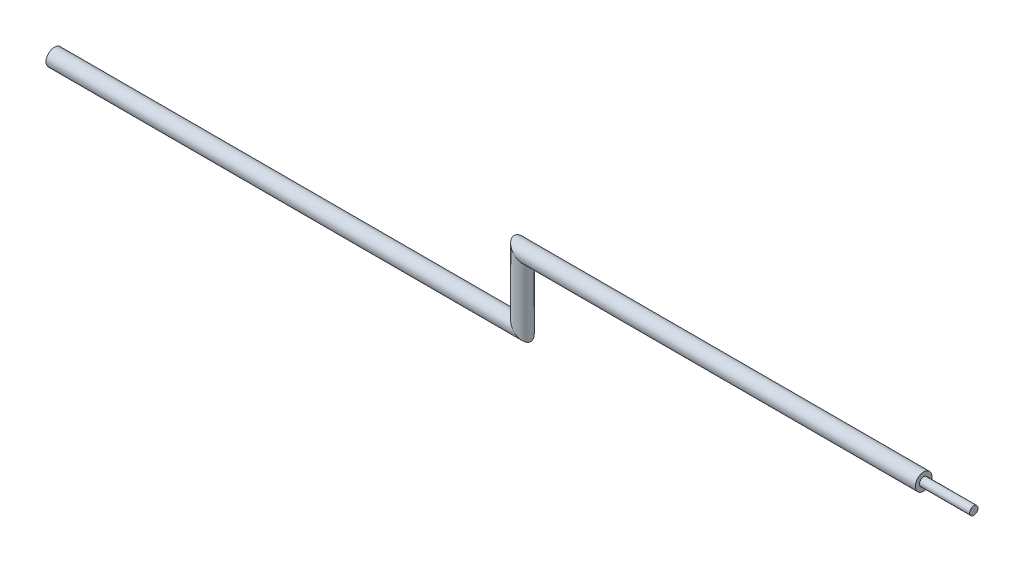
SolidWorks part; units mm, degrees
ref_plane "Front Plane" through (0, 0, 0) normal (0, 0, 1) x (1, 0, 0)
ref_plane "Top Plane" through (0, 0, 0) normal (0, 1, 0) x (1, 0, 0)
ref_plane "Right Plane" through (0, 0, 0) normal (1, 0, 0) x (0, 0, -1)
sketch "Sketch1" plane through (0, 0, 0) normal (0, 0, 1) x (1, 0, 0)
  line L0 (355.6, 0) -> (0, 0)
  line L1 (355.6, 0) -> (355.6, 50.8)
  line L2 (355.6, 50.8) -> (660.4, 50.8)
  point P4 (0, 0)
  dimension "D1" = 355.6
  dimension "D2" = 50.8
  dimension "D3" = 304.8
sweep "Sweep1" add path "Sketch1" circular profile diameter 12.7 parameters "D3"=12.7
sketch "Sketch20" plane through (660.4, 0, 0) normal (1, 0, 0) x (0, 0, -1)
  circle A0 centre (0, 50.8) radius 3.175
  circle A1 centre (0, 50.8) radius 6.35 construction
  dimension "D1" = 6.35
extrude "Boss-Extrude3" add sketch "Sketch20" along normal blind 38.1
